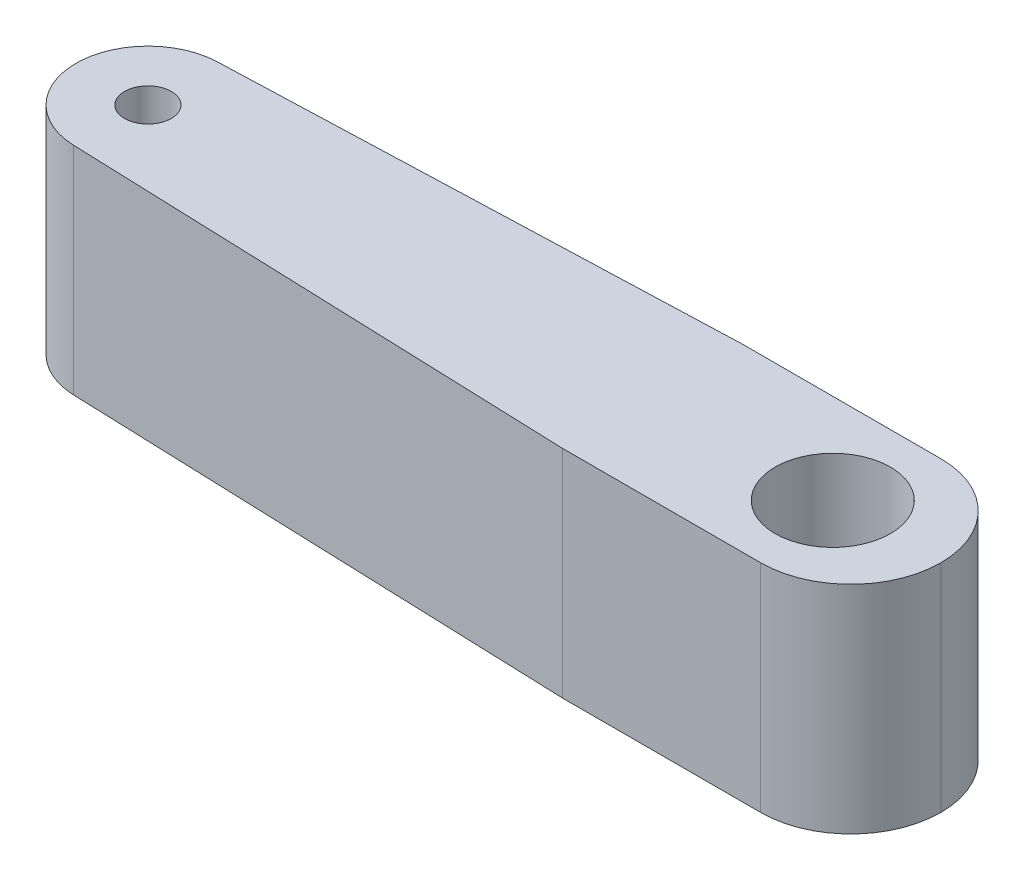
SolidWorks part; units mm, degrees
ref_plane "前视基准面" through (0, 0, 0) normal (0, 0, 1) x (1, 0, 0)
ref_plane "上视基准面" through (0, 0, 0) normal (0, 1, 0) x (1, 0, 0)
ref_plane "右视基准面" through (0, 0, 0) normal (1, 0, 0) x (0, 0, -1)
sketch "草图1" plane through (0, 0, 0) normal (0, 1, 0) x (1, 0, 0)
  line L1 (-12.5, 2.5) -> (12.5, 2.5)
  line L2 (-12.5, 2.5) -> (-12.5, -2.5)
  line L3 (-12.5, -2.5) -> (12.5, -2.5)
  line L4 (12.5, 2.5) -> (12.5, -2.5)
  line L5 (-12.5, 2.5) -> (12.5, -2.5) construction
  line L6 (-12.5, -2.5) -> (12.5, 2.5) construction
  point P0 (0, 0)
  dimension "D1" = 25
  dimension "D2" = 5
extrude "凸台-拉伸1" add sketch "草图1" along normal blind 6
sketch "草图2" plane through (0, 6, 0) normal (0, 1, 0) x (1, 0, 0)
  line L4 (12.5, -2.5) -> (12.5, 2.5)
  line L5 (12.5, 2.5) -> (-12.5, 2.5)
  line L6 (-12.5, 2.5) -> (-12.5, -2.5)
  line L7 (-12.5, -2.5) -> (12.5, -2.5)
  line L8 (12.5, -2.5) -> (12.5, 2.5)
  line L9 (12.5, 2.5) -> (-12.5, 2.5)
  line L10 (-12.5, 2.5) -> (-12.5, -2.5)
  line L11 (-12.5, -2.5) -> (12.5, -2.5)
  circle A0 centre (9.5, 0) radius 1.6
  circle A1 centre (-9.5, 0) radius 0.65
  dimension "D2" = 3
  dimension "D4" = 3.2
  dimension "D5" = 1.3
  dimension "D3" = 3
  dimension "D1" = 0
extrude "切除-拉伸1" cut sketch "草图2" against normal blind 10 contours A0 | A1
fillet "圆角1" radius 2.5 4 edges at (12.5, 3, 2.5) (12.5, 3, -2.5) (-12.5, 3, 2.5) (-12.5, 3, -2.5)
sketch "草图3" plane through (0, 6, 0) normal (0, 1, 0) x (1, 0, 0)
  line L0 (4.5, 2.5) -> (4.5, -2.5)
  line L1 (10, 2.5) -> (-10, 2.5) construction
  line L2 (-10, -2.5) -> (10, -2.5) construction
  line L3 (4.5, 2.5) -> (-9.5712, 1.9987)
  line L4 (4.5, -2.5) -> (-9.5712, -1.9987)
  circle A0 centre (-9.5, 0) radius 0.65 construction
  circle A1 centre (-9.5, 0) radius 0.65
  circle A2 centre (-9.5, 0) radius 2
  line M4 (-10, -2.5) -> (10, -2.5)
  line M7 (10, 2.5) -> (-10, 2.5)
  arc M8 (-10, 2.5) -> (-12.5, 0) centre (-10, 0) ccw
  arc M9 (-12.5, 0) -> (-10, -2.5) centre (-10, 0) ccw
  dimension "D1" = 14
extrude "切除-拉伸2" cut sketch "草图3" against normal blind 7 contours A2 L3 L4 M7 M8 M9 M4 region at (-2.5419, 6, -2.4265) body kept at (4.5, 0, -2.5)
